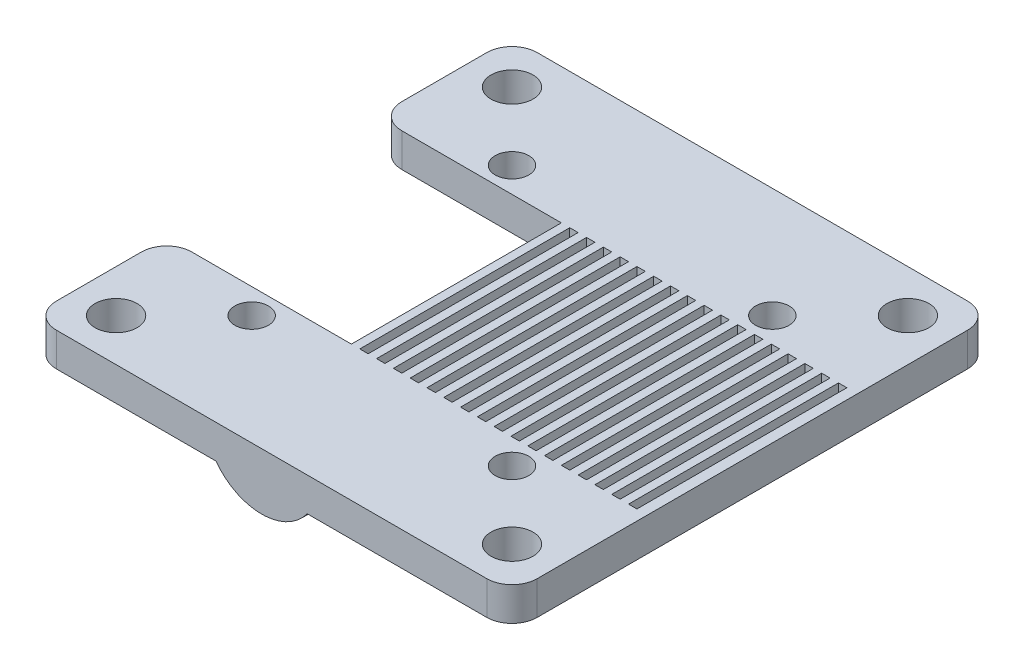
SolidWorks part; units mm, degrees
material "ABS"
ref_plane "Front Plane" through (0, 0, 0) normal (0, 0, 1) x (1, 0, 0)
ref_plane "Top Plane" through (0, 0, 0) normal (0, 1, 0) x (1, 0, 0)
ref_plane "Right Plane" through (0, 0, 0) normal (1, 0, 0) x (0, 0, -1)
sketch "Sketch1" plane through (0, 0, 0) normal (0, 1, 0) x (1, 0, 0)
  line L1 (25.625, 28.625) -> (-25.625, 28.625)
  line L2 (28.625, 25.625) -> (28.625, -25.625)
  line L3 (25.625, -28.625) -> (-25.625, -28.625)
  line L4 (-28.625, 25.625) -> (-28.625, -25.625)
  line L5 (28.625, 28.625) -> (-28.625, -28.625) construction
  line L6 (28.625, -28.625) -> (-28.625, 28.625) construction
  line L7 (23.57, -23.57) -> (-23.57, -23.57) construction
  line L8 (23.57, -23.57) -> (23.57, 23.57) construction
  line L9 (23.57, 23.57) -> (-23.57, 23.57) construction
  line L10 (-23.57, -23.57) -> (-23.57, 23.57) construction
  line L11 (23.57, -23.57) -> (-23.57, 23.57) construction
  line L12 (23.57, 23.57) -> (-23.57, -23.57) construction
  line L13 (15.5, 15.5) -> (-15.5, 15.5) construction
  line L14 (15.5, 15.5) -> (15.5, -15.5) construction
  line L15 (15.5, -15.5) -> (-15.5, -15.5) construction
  line L16 (-15.5, 15.5) -> (-15.5, -15.5) construction
  line L17 (15.5, 15.5) -> (-15.5, -15.5) construction
  line L18 (15.5, -15.5) -> (-15.5, 15.5) construction
  circle A0 centre (-15.5, 15.5) radius 2
  circle A1 centre (-23.57, 23.57) radius 2.5
  circle A2 centre (23.57, 23.57) radius 2.5
  circle A3 centre (15.5, 15.5) radius 2
  circle A4 centre (15.5, -15.5) radius 2
  circle A5 centre (-15.5, -15.5) radius 2
  circle A6 centre (-23.57, -23.57) radius 2.5
  circle A7 centre (23.57, -23.57) radius 2.5
  arc A8 (25.625, 28.625) -> (28.625, 25.625) centre (25.625, 25.625) cw
  arc A9 (28.625, -25.625) -> (25.625, -28.625) centre (25.625, -25.625) cw
  arc A10 (-25.625, -28.625) -> (-28.625, -25.625) centre (-25.625, -25.625) cw
  arc A11 (-25.625, 28.625) -> (-28.625, 25.625) centre (-25.625, 25.625) ccw
  point P0 (0, 0)
  point P5 (0, 0)
  point P11 (0, 0)
  dimension "D7" = 5
  dimension "D8" = 5
  dimension "D9" = 4
  dimension "D10" = 4
  dimension "D11" = 4
  dimension "D12" = 4
  dimension "D13" = 5
  dimension "D14" = 5
  dimension "D15" = 3
  dimension "D1" = 57.25
  dimension "D2" = 57.25
  dimension "D3" = 47.14
  dimension "D4" = 47.14
  dimension "D5" = 31
  dimension "D6" = 31
extrude "Boss-Extrude1" add sketch "Sketch1" along normal blind 4
sketch "Sketch2" plane through (0, 4, 0) normal (0, 1, 0) x (1, 0, 0)
  line L0 (-28.625, 25.625) -> (-28.625, -25.625) construction
  line L3 (-27.625, 12.5) -> (-26.625, 12.5)
  line L4 (-27.625, 12.5) -> (-27.625, -12.5)
  line L5 (-27.625, -12.5) -> (-26.625, -12.5)
  line L6 (-26.625, 12.5) -> (-26.625, -12.5)
  line L7 (-25.625, -12.5) -> (-24.625, -12.5)
  line L8 (-24.625, 12.5) -> (-24.625, -12.5)
  line L9 (-25.625, 12.5) -> (-25.625, -12.5)
  line L10 (-25.625, 12.5) -> (-24.625, 12.5)
  line L11 (-23.625, -12.5) -> (-22.625, -12.5)
  line L12 (-22.625, 12.5) -> (-22.625, -12.5)
  line L13 (-23.625, 12.5) -> (-23.625, -12.5)
  line L14 (-23.625, 12.5) -> (-22.625, 12.5)
  line L15 (-21.625, -12.5) -> (-20.625, -12.5)
  line L16 (-20.625, 12.5) -> (-20.625, -12.5)
  line L17 (-21.625, 12.5) -> (-21.625, -12.5)
  line L18 (-21.625, 12.5) -> (-20.625, 12.5)
  line L19 (-19.625, -12.5) -> (-18.625, -12.5)
  line L20 (-18.625, 12.5) -> (-18.625, -12.5)
  line L21 (-19.625, 12.5) -> (-19.625, -12.5)
  line L22 (-19.625, 12.5) -> (-18.625, 12.5)
  line L23 (-17.625, -12.5) -> (-16.625, -12.5)
  line L24 (-16.625, 12.5) -> (-16.625, -12.5)
  line L25 (-17.625, 12.5) -> (-17.625, -12.5)
  line L26 (-17.625, 12.5) -> (-16.625, 12.5)
  line L27 (-15.625, -12.5) -> (-14.625, -12.5)
  line L28 (-14.625, 12.5) -> (-14.625, -12.5)
  line L29 (-15.625, 12.5) -> (-15.625, -12.5)
  line L30 (-15.625, 12.5) -> (-14.625, 12.5)
  line L31 (-13.625, -12.5) -> (-12.625, -12.5)
  line L32 (-12.625, 12.5) -> (-12.625, -12.5)
  line L33 (-13.625, 12.5) -> (-13.625, -12.5)
  line L34 (-13.625, 12.5) -> (-12.625, 12.5)
  line L35 (-11.625, -12.5) -> (-10.625, -12.5)
  line L36 (-10.625, 12.5) -> (-10.625, -12.5)
  line L37 (-11.625, 12.5) -> (-11.625, -12.5)
  line L38 (-11.625, 12.5) -> (-10.625, 12.5)
  line L39 (-9.625, -12.5) -> (-8.625, -12.5)
  line L40 (-8.625, 12.5) -> (-8.625, -12.5)
  line L41 (-9.625, 12.5) -> (-9.625, -12.5)
  line L42 (-9.625, 12.5) -> (-8.625, 12.5)
  line L43 (-7.625, -12.5) -> (-6.625, -12.5)
  line L44 (-6.625, 12.5) -> (-6.625, -12.5)
  line L45 (-7.625, 12.5) -> (-7.625, -12.5)
  line L46 (-7.625, 12.5) -> (-6.625, 12.5)
  line L47 (-5.625, -12.5) -> (-4.625, -12.5)
  line L48 (-4.625, 12.5) -> (-4.625, -12.5)
  line L49 (-5.625, 12.5) -> (-5.625, -12.5)
  line L50 (-5.625, 12.5) -> (-4.625, 12.5)
  line L51 (-3.625, -12.5) -> (-2.625, -12.5)
  line L52 (-2.625, 12.5) -> (-2.625, -12.5)
  line L53 (-3.625, 12.5) -> (-3.625, -12.5)
  line L54 (-3.625, 12.5) -> (-2.625, 12.5)
  line L55 (-1.625, -12.5) -> (-0.625, -12.5)
  line L56 (-0.625, 12.5) -> (-0.625, -12.5)
  line L57 (-1.625, 12.5) -> (-1.625, -12.5)
  line L58 (-1.625, 12.5) -> (-0.625, 12.5)
  line L59 (0.375, -12.5) -> (1.375, -12.5)
  line L60 (1.375, 12.5) -> (1.375, -12.5)
  line L61 (0.375, 12.5) -> (0.375, -12.5)
  line L62 (0.375, 12.5) -> (1.375, 12.5)
  line L63 (2.375, -12.5) -> (3.375, -12.5)
  line L64 (3.375, 12.5) -> (3.375, -12.5)
  line L65 (2.375, 12.5) -> (2.375, -12.5)
  line L66 (2.375, 12.5) -> (3.375, 12.5)
  line L67 (4.375, -12.5) -> (5.375, -12.5)
  line L68 (5.375, 12.5) -> (5.375, -12.5)
  line L69 (4.375, 12.5) -> (4.375, -12.5)
  line L70 (4.375, 12.5) -> (5.375, 12.5)
  line L71 (6.375, -12.5) -> (7.375, -12.5)
  line L72 (7.375, 12.5) -> (7.375, -12.5)
  line L73 (6.375, 12.5) -> (6.375, -12.5)
  line L74 (6.375, 12.5) -> (7.375, 12.5)
  line L75 (8.375, -12.5) -> (9.375, -12.5)
  line L76 (9.375, 12.5) -> (9.375, -12.5)
  line L77 (8.375, 12.5) -> (8.375, -12.5)
  line L78 (8.375, 12.5) -> (9.375, 12.5)
  line L79 (10.375, -12.5) -> (11.375, -12.5)
  line L80 (11.375, 12.5) -> (11.375, -12.5)
  line L81 (10.375, 12.5) -> (10.375, -12.5)
  line L82 (10.375, 12.5) -> (11.375, 12.5)
  line L83 (12.375, -12.5) -> (13.375, -12.5)
  line L84 (13.375, 12.5) -> (13.375, -12.5)
  line L85 (12.375, 12.5) -> (12.375, -12.5)
  line L86 (12.375, 12.5) -> (13.375, 12.5)
  line L87 (14.375, -12.5) -> (15.375, -12.5)
  line L88 (15.375, 12.5) -> (15.375, -12.5)
  line L89 (14.375, 12.5) -> (14.375, -12.5)
  line L90 (14.375, 12.5) -> (15.375, 12.5)
  line L91 (16.375, -12.5) -> (17.375, -12.5)
  line L92 (17.375, 12.5) -> (17.375, -12.5)
  line L93 (16.375, 12.5) -> (16.375, -12.5)
  line L94 (16.375, 12.5) -> (17.375, 12.5)
  line L95 (18.375, -12.5) -> (19.375, -12.5)
  line L96 (19.375, 12.5) -> (19.375, -12.5)
  line L97 (18.375, 12.5) -> (18.375, -12.5)
  line L98 (18.375, 12.5) -> (19.375, 12.5)
  line L99 (20.375, -12.5) -> (21.375, -12.5)
  line L100 (21.375, 12.5) -> (21.375, -12.5)
  line L101 (20.375, 12.5) -> (20.375, -12.5)
  line L102 (20.375, 12.5) -> (21.375, 12.5)
  line L103 (22.375, -12.5) -> (23.375, -12.5)
  line L104 (23.375, 12.5) -> (23.375, -12.5)
  line L105 (22.375, 12.5) -> (22.375, -12.5)
  line L106 (22.375, 12.5) -> (23.375, 12.5)
  line L107 (24.375, -12.5) -> (25.375, -12.5)
  line L108 (25.375, 12.5) -> (25.375, -12.5)
  line L109 (24.375, 12.5) -> (24.375, -12.5)
  line L110 (24.375, 12.5) -> (25.375, 12.5)
  line L111 (26.375, -12.5) -> (27.375, -12.5)
  line L112 (27.375, 12.5) -> (27.375, -12.5)
  line L113 (26.375, 12.5) -> (26.375, -12.5)
  line L114 (26.375, 12.5) -> (27.375, 12.5)
  dimension "D1" = 1
  dimension "D2" = 1
  dimension "D3" = 12.5
  dimension "D4" = 25
  dimension "D5" = 28
extrude "Cut-Extrude1" cut sketch "Sketch2" against normal blind 1
sketch "Sketch3" plane through (0, 0, 0) normal (0, -1, 0) x (1, 0, 0)
  line L0 (-28.625, -25.625) -> (-28.625, 25.625) construction
  line L1 (-28.625, -12.5) -> (-6.625, -12.5)
  line L2 (-28.625, -12.5) -> (-28.625, 12.5)
  line L3 (-28.625, 12.5) -> (-6.625, 12.5)
  line L4 (-6.625, -12.5) -> (-6.625, 12.5)
  dimension "D1" = 25
  dimension "D2" = 22
  dimension "D3" = 12.5
extrude "Cut-Extrude2" cut sketch "Sketch3" against normal through all
sketch "Sketch4" plane through (0, 0, -28.625) normal (0, 0, -1) x (-1, 0, 0)
  line L1 (-4.2493, 0) -> (6.625, 0)
  line L3 (-25.625, 0) -> (25.625, 0) construction
  line L4 (-25.625, 4) -> (25.625, 4) construction
  arc A0 (-4.2493, 0) -> (6.625, 0) centre (1.1879, 4) ccw
  dimension "D1" = 13.5
  dimension "D2" = 22
extrude "Boss-Extrude2" add sketch "Sketch4" against normal up to surface (57.25 mm away) up to face at (0, 2, 28.625)
fillet "Fillet1" radius 3 2 edges at (-28.625, 2, 12.5) (-28.625, 2, -12.5)
